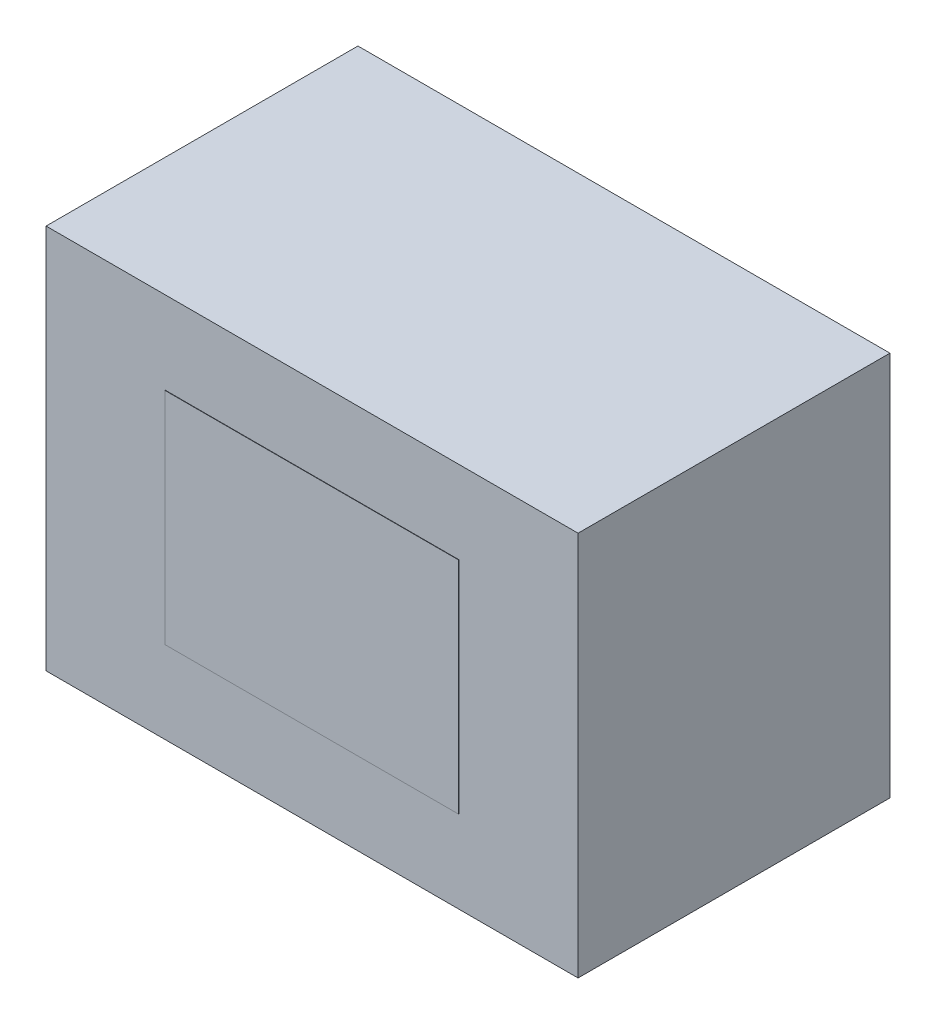
SolidWorks part; units mm, degrees
ref_plane "Front" through (0, 0, 0) normal (0, 0, 1) x (1, 0, 0)
ref_plane "Top" through (0, 0, 0) normal (0, 1, 0) x (1, 0, 0)
ref_plane "Right" through (0, 0, 0) normal (1, 0, 0) x (0, 0, -1)
sketch "Sketch1" plane through (0, 0, 0) normal (0, 0, 1) x (1, 0, 0)
  line L1 (88.9, -63.5) -> (-88.9, -63.5)
  line L2 (88.9, -63.5) -> (88.9, 63.5)
  line L3 (88.9, 63.5) -> (-88.9, 63.5)
  line L4 (-88.9, -63.5) -> (-88.9, 63.5)
  line L5 (88.9, -63.5) -> (-88.9, 63.5) construction
  line L6 (88.9, 63.5) -> (-88.9, -63.5) construction
  point P0 (0, 0)
  dimension "D1" = 177.8
  dimension "D2" = 127
extrude "Boss-Extrude1" add sketch "Sketch1" along normal blind 101.6
other "Move Face1" face at (0, -63.5, 50.8) face at (0, 0, 0) face at (-88.9, 0, 50.8) face at (88.9, 0, 50.8) face at (0, 63.5, 50.8) face at (0, 0, 101.6) offset 3.175 parameters "D1"=3.175
sketch "Sketch2" plane through (0, 0, 104.775) normal (0, 0, 1) x (1, 0, 0)
  line L1 (-50.8, -38.1) -> (50.8, -38.1)
  line L2 (-50.8, -38.1) -> (-50.8, 38.1)
  line L3 (-50.8, 38.1) -> (50.8, 38.1)
  line L4 (50.8, -38.1) -> (50.8, 38.1)
  line L5 (-50.8, -38.1) -> (50.8, 38.1) construction
  line L6 (-50.8, 38.1) -> (50.8, -38.1) construction
  point P0 (0, 0)
  dimension "D1" = 76.2
  dimension "D2" = 101.6
extrude "Boss-Extrude2" add sketch "Sketch2" along normal blind 0.127
